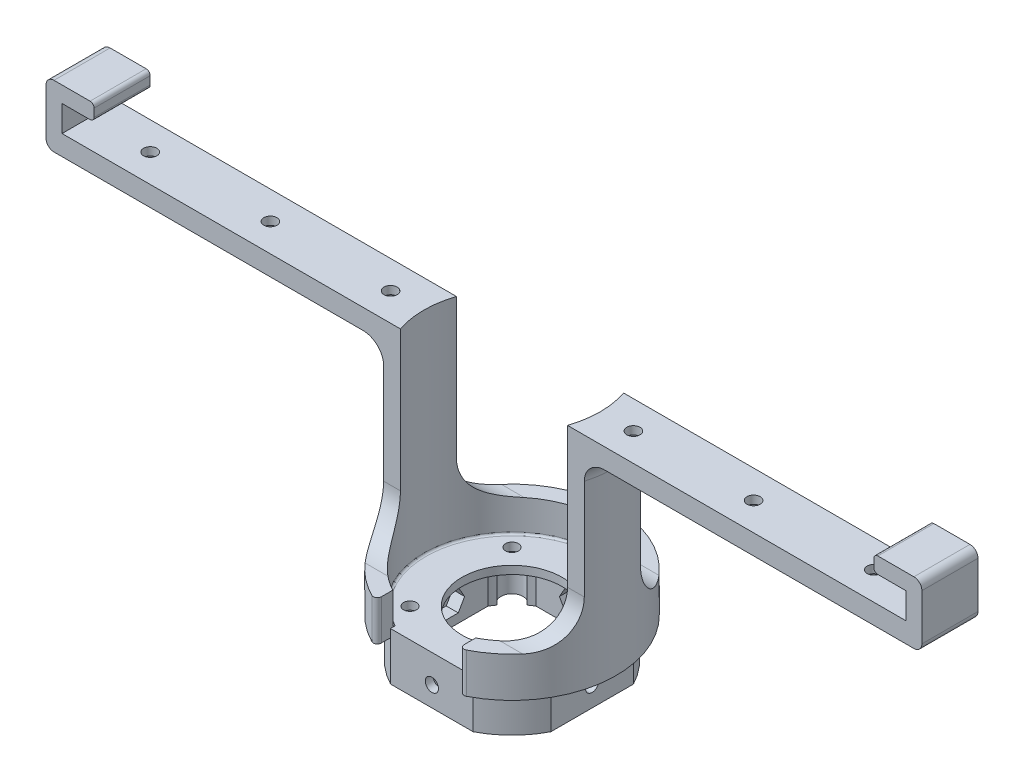
SolidWorks part; units mm, degrees
ref_plane "前视基准面" through (0, 0, 0) normal (0, 0, 1) x (1, 0, 0)
ref_plane "上视基准面" through (0, 0, 0) normal (0, 1, 0) x (1, 0, 0)
ref_plane "右视基准面" through (0, 0, 0) normal (1, 0, 0) x (0, 0, -1)
sketch "草图1" plane through (0, 0, 0) normal (0, 1, 0) x (1, 0, 0)
  line L0 (0, 0) -> (0, 18) construction
  line L1 (0, 0) -> (12.7279, 12.7279) construction
  line L2 (-32.6893, 0) -> (36.6315, 0) construction
  arc A0 (-20.3411, 8.381) -> (20.3411, 8.381) centre (0, 0) ccw
  circle A1 centre (0, 0) radius 18 construction
  circle A2 centre (12.7279, 12.7279) radius 1.6
  circle A3 centre (12.7279, -12.7279) radius 1.6
  circle A4 centre (-12.7279, -12.7279) radius 1.6
  circle A5 centre (-12.7279, 12.7279) radius 1.6
  circle A6 centre (0, 0) radius 22
  arc A7 (20.3411, 8.381) -> (-20.3411, 8.381) centre (0, 0) ccw
  point P16 (0, 0)
  dimension "D1" = 44
  dimension "D2" = 36
  dimension "D3" = 45
  dimension "D4" = 3.2
  dimension "D5" = 4
extrude "凸台-拉伸1" add sketch "草图1" along normal blind 2 contours A0 A6 A2 A3 A4 A5 region at (0, 0, 0)
sketch "草图2" plane through (0, 2, 0) normal (0, 1, 0) x (1, 0, 0)
  circle A1 centre (0, 0) radius 12.5
  dimension "D1" = 25
extrude "切除-拉伸1" cut sketch "草图2" against normal blind 3 contours A1 region at (0, 2, 0)
sketch "草图5" plane through (0, 0, 0) normal (0, 1, 0) x (1, 0, 0)
  line L6 (0, 27.5) -> (0, -27.5) construction
  circle A1 centre (0, 0) radius 22
  circle A3 centre (0, 0) radius 26
  dimension "D3" = 44
  dimension "D1" = 52
extrude "凸台-拉伸3" add sketch "草图5" along normal blind 10
sketch "草图14" plane through (0, 0, 0) normal (0, -1, 0) x (1, 0, 0)
  line L0 (-10.3078, 20) -> (10.3078, 20)
  line L1 (20, 10.3078) -> (20, -10.3078)
  line L2 (-10.3078, -20) -> (10.3078, -20)
  line L3 (-20, -10.3078) -> (-20, 10.3078)
  line L4 (-9.0139, 15) -> (9.0139, 15)
  line L5 (15, 9.0139) -> (15, -9.0139)
  line L6 (-15, 9.0139) -> (-15, -9.0139)
  line L7 (-9.0139, -15) -> (9.0139, -15)
  arc A0 (-10.3078, 20) -> (-20, 10.3078) centre (0, 0) ccw
  arc A1 (20, 10.3078) -> (10.3078, 20) centre (0, 0) ccw
  arc A2 (10.3078, -20) -> (20, -10.3078) centre (0, 0) ccw
  arc A3 (-20, -10.3078) -> (-10.3078, -20) centre (0, 0) ccw
  arc A4 (-15, -9.0139) -> (-14.1106, -10.3508) centre (0, 0) ccw
  arc A5 (-9.0139, 15) -> (-10.3508, 14.1106) centre (0, 0) ccw
  arc A6 (15, 9.0139) -> (14.1106, 10.3508) centre (0, 0) ccw
  arc A7 (9.0139, -15) -> (10.3508, -14.1106) centre (0, 0) ccw
  arc A8 (-10.3508, 14.1106) -> (-14.1106, 10.3508) centre (-12.7279, 12.7279) ccw
  arc A9 (14.1106, 10.3508) -> (10.3508, 14.1106) centre (12.7279, 12.7279) ccw
  arc A10 (-14.1106, -10.3508) -> (-10.3508, -14.1106) centre (-12.7279, -12.7279) ccw
  arc A11 (10.3508, -14.1106) -> (14.1106, -10.3508) centre (12.7279, -12.7279) ccw
  arc A12 (-14.1106, 10.3508) -> (-15, 9.0139) centre (0, 0) ccw
  arc A13 (10.3508, 14.1106) -> (9.0139, 15) centre (0, 0) ccw
  arc A14 (-10.3508, -14.1106) -> (-9.0139, -15) centre (0, 0) ccw
  arc A15 (14.1106, -10.3508) -> (15, -9.0139) centre (0, 0) ccw
  dimension "D1" = 45
  dimension "D6" = 35
  dimension "D11" = 5.5
  dimension "D12" = 5.5
  dimension "D13" = 5.5
  dimension "D14" = 5.5
  dimension "D2" = 20
  dimension "D3" = 20
  dimension "D4" = 20
  dimension "D5" = 20
  dimension "D7" = 5
  dimension "D8" = 5
  dimension "D9" = 5
  dimension "D10" = 5
extrude "凸台-拉伸5" add sketch "草图14" along normal blind 10
sketch "草图15" plane through (-20, 0, 0) normal (-1, 0, 0) x (0, 0, 1)
  line L0 (10.3078, 0) -> (-10.3078, 0) construction
  line L3 (0, 0) -> (0, -10) construction
  line L4 (10.3078, -10) -> (-10.3078, -10) construction
  circle A0 centre (0, -5) radius 1.65
  dimension "D1" = 3.3
  dimension "D2" = 5
extrude "切除-拉伸2" cut sketch "草图15" against normal blind 42
sketch "草图16" plane through (0, 0, -20) normal (0, 0, -1) x (-1, 0, 0)
  line L0 (10.3078, 0) -> (-10.3078, 0) construction
  line L1 (0, 0) -> (0, -10) construction
  line L2 (10.3078, -10) -> (-10.3078, -10) construction
  circle A0 centre (0, -5) radius 1.65
  dimension "D1" = 3.3
  dimension "D2" = 5
extrude "切除-拉伸3" cut sketch "草图16" against normal blind 42
sketch "草图18" plane through (0, 0, 0) normal (0, 0, 1) x (1, 0, 0)
  line L1 (-1.5877, -2.25) -> (-3.1754, -5)
  line L2 (-3.1754, -5) -> (-1.5877, -7.75)
  line L3 (-1.5877, -7.75) -> (1.5877, -7.75)
  line L4 (1.5877, -7.75) -> (3.1754, -5)
  line L5 (3.1754, -5) -> (1.5877, -2.25)
  line L6 (1.5877, -2.25) -> (-1.5877, -2.25)
  circle A0 centre (0, -5) radius 2.75 construction
  dimension "D1" = 5.5
extrude "切除-拉伸4" cut sketch "草图18" against normal mid plane 36
sketch "草图19" plane through (0, 0, 0) normal (1, 0, 0) x (0, 0, -1)
  line L1 (-1.5877, -2.25) -> (-3.1754, -5)
  line L2 (-3.1754, -5) -> (-1.5877, -7.75)
  line L3 (-1.5877, -7.75) -> (1.5877, -7.75)
  line L4 (1.5877, -7.75) -> (3.1754, -5)
  line L5 (3.1754, -5) -> (1.5877, -2.25)
  line L6 (1.5877, -2.25) -> (-1.5877, -2.25)
  circle A0 centre (0, -5) radius 2.75 construction
  dimension "D1" = 5.5
extrude "切除-拉伸5" cut sketch "草图19" against normal mid plane 36
sketch "草图23" plane through (0, 10, 0) normal (0, 1, 0) x (1, 0, 0)
  line L0 (-20.8567, 7) -> (-25.04, 7)
  line L1 (-26, 0) -> (26, 0) construction
  line L2 (-20.8567, -7) -> (-25.04, -7)
  line L3 (20.8567, 7) -> (25.04, 7)
  line L4 (20.8567, -7) -> (25.04, -7)
  circle A0 centre (0, 0) radius 22 construction
  circle A1 centre (0, 0) radius 26 construction
  circle A2 centre (0, 0) radius 26
  circle A3 centre (0, 0) radius 22 construction
  circle A4 centre (0, 0) radius 22
  circle M8 centre (0, 0) radius 26
  circle M9 centre (0, 0) radius 22
  dimension "D1" = 7
  dimension "D2" = 7
  dimension "D3" = 7
extrude "凸台-拉伸6" add sketch "草图23" along normal blind 45 contours L1 A4 L0 M8 | L1 A2 L2 M9 | L1 A2 L3 M9 | L1 A4 L4 M8 region at (-23.6485, 10, -3.526) region at (23.6485, 10, -3.526) region at (-23.6485, 10, 3.526) region at (23.6485, 10, 3.526)
sketch "草图24" plane through (0, 55, 0) normal (0, 1, 0) x (1, 0, 0)
  line L0 (-20.8567, 7) -> (-25.04, 7) construction
  line L1 (-25.04, -7) -> (-75.3, -7)
  line L2 (-25.04, -7) -> (-25.04, 7)
  line L3 (-25.04, 7) -> (-75.3, 7)
  line L4 (-75.3, -7) -> (-75.3, 7)
  dimension "D1" = 50.26
extrude "凸台-拉伸7" add sketch "草图24" against normal blind 5
mirror "镜向1" about plane through (0, 0, 0) normal (1, 0, 0) of "凸台-拉伸7"
sketch "草图25" plane through (0, 55, 0) normal (0, 1, 0) x (1, 0, 0)
  line L0 (-75.3, 7) -> (-75.3, -7) construction
  line L2 (-22, 0) -> (-75.3, 0) construction
  circle A0 centre (-60.3, 0) radius 1.65
  arc A1 (-20.8567, 7) -> (-20.8567, -7) centre (0, 0) ccw construction
  circle A2 centre (-30.3, 0) radius 1.65
  dimension "D1" = 3.3
  dimension "D3" = 3.3
  dimension "D2" = 15
  dimension "D4" = 30
extrude "切除-拉伸6" cut sketch "草图25" against normal blind 5
sketch "草图26" plane through (0, 50, 0) normal (0, 1, 0) x (1, 0, 0)
  line L1 (-58.7123, 2.75) -> (-61.8877, 2.75)
  line L2 (-61.8877, 2.75) -> (-63.4754, 0)
  line L3 (-63.4754, 0) -> (-61.8877, -2.75)
  line L4 (-61.8877, -2.75) -> (-58.7123, -2.75)
  line L5 (-58.7123, -2.75) -> (-57.1245, 0)
  line L6 (-57.1245, 0) -> (-58.7123, 2.75)
  line L7 (-31.8877, 2.75) -> (-33.4754, 0)
  line L8 (-33.4754, 0) -> (-31.8877, -2.75)
  line L9 (-31.8877, -2.75) -> (-28.7123, -2.75)
  line L10 (-28.7123, -2.75) -> (-27.1245, 0)
  line L11 (-27.1245, 0) -> (-28.7123, 2.75)
  line L12 (-28.7123, 2.75) -> (-31.8877, 2.75)
  circle A0 centre (-60.3, 0) radius 2.75 construction
  circle A1 centre (-30.3, 0) radius 2.75 construction
  dimension "D1" = 5.5
  dimension "D2" = 5.5
extrude "切除-拉伸7" cut sketch "草图26" along normal blind 3
mirror "镜向3" about plane through (0, 0, 0) normal (1, 0, 0) of "切除-拉伸6", "切除-拉伸7"
sketch "草图28" plane through (0, 0, 0) normal (0, -1, 0) x (1, 0, 0)
  line L0 (-10.34, 20) -> (10.34, 20)
  line L1 (10.3078, 20) -> (-10.3078, 20) construction
  line L2 (10.34, 20) -> (10.34, 23.8555)
  line L3 (-10.34, 20) -> (-10.34, 23.8555)
  line L4 (0, 26) -> (0, -26) construction
  line L5 (-26, 0) -> (26, 0) construction
  circle A0 centre (0, 0) radius 26 construction
  arc A2 (10.34, 23.8555) -> (-10.34, 23.8555) centre (0, 0) ccw
  point P4 (0, 20)
  dimension "D1" = 20.68
extrude "切除-拉伸9" cut sketch "草图28" against normal blind 10
sketch "草图29" plane through (0, 10, 0) normal (0, 1, 0) x (1, 0, 0)
  line L6 (-10.34, -20) -> (-10.34, -19.4187)
  line L7 (10.34, -20) -> (10.34, -19.4187)
  line L8 (9.1652, -20) -> (10.34, -20) construction
  line L9 (9.1652, -20) -> (10.34, -20)
  line L10 (-10.34, -20) -> (-9.1652, -20) construction
  line L11 (-10.34, -20) -> (-9.1652, -20)
  circle A6 centre (0, 0) radius 22 construction
  circle A7 centre (0, 0) radius 22 construction
  arc A8 (-10.34, -19.4187) -> (-9.1652, -20) centre (0, 0) ccw
  arc A9 (9.1652, -20) -> (10.34, -19.4187) centre (0, 0) ccw
extrude "切除-拉伸10" cut sketch "草图29" against normal blind 8
sketch "草图34" plane through (0, 50, 0) normal (0, -1, 0) x (1, 0, 0)
  line L0 (-75.3, 0) -> (75.3, 0) construction
  line L1 (-75.3, -7) -> (-105.3, -7)
  line L2 (-75.3, -7) -> (-75.3, 7)
  line L3 (-75.3, 7) -> (-105.3, 7)
  line L4 (-105.3, -7) -> (-105.3, 7)
  line L5 (75.3, -7) -> (105.3, -7)
  line L6 (75.3, -7) -> (75.3, 7)
  line L7 (75.3, 7) -> (105.3, 7)
  line L8 (105.3, -7) -> (105.3, 7)
  line L9 (-75.3, -7) -> (-75.3, 7) construction
  line L10 (75.3, -7) -> (75.3, 7) construction
  line L12 (-75.3, 7) -> (-25.04, 7) construction
  line L13 (75.3, 7) -> (25.04, 7) construction
  point P14 (-75.3, 0)
  point P17 (75.3, 0)
  dimension "D1" = 30
  dimension "D2" = 30
extrude "凸台-拉伸9" add sketch "草图34" against normal blind 5
sketch "草图35" plane through (0, 55, 0) normal (0, 1, 0) x (1, 0, 0)
  circle A0 centre (-90.3, 0) radius 1.65
  circle A1 centre (90.3, 0) radius 1.65
  circle A2 centre (-60.3, 0) radius 1.65 construction
  circle A3 centre (60.3, 0) radius 1.65 construction
  dimension "D3" = 3.3
  dimension "D4" = 3.3
  dimension "D1" = 30
  dimension "D2" = 30
extrude "切除-拉伸11" cut sketch "草图35" against normal blind 5
sketch "草图36" plane through (0, 50, 0) normal (0, -1, 0) x (1, 0, 0)
  line L1 (-91.8877, 2.75) -> (-93.4754, 0)
  line L2 (-93.4754, 0) -> (-91.8877, -2.75)
  line L3 (-91.8877, -2.75) -> (-88.7123, -2.75)
  line L4 (-88.7123, -2.75) -> (-87.1245, 0)
  line L5 (-87.1245, 0) -> (-88.7123, 2.75)
  line L6 (-88.7123, 2.75) -> (-91.8877, 2.75)
  line L7 (91.8877, 2.75) -> (88.7123, 2.75)
  line L8 (88.7123, 2.75) -> (87.1245, 0)
  line L9 (87.1245, 0) -> (88.7123, -2.75)
  line L10 (88.7123, -2.75) -> (91.8877, -2.75)
  line L11 (91.8877, -2.75) -> (93.4754, 0)
  line L12 (93.4754, 0) -> (91.8877, 2.75)
  circle A0 centre (-90.3, 0) radius 2.75 construction
  circle A1 centre (90.3, 0) radius 2.75 construction
  dimension "D1" = 5.5
  dimension "D2" = 5.5
extrude "切除-拉伸12" cut sketch "草图36" against normal blind 3
sketch "草图37" plane through (0, 50, 0) normal (0, -1, 0) x (1, 0, 0)
  line L0 (-105.3, 7) -> (-25.04, 7) construction
  line L1 (-105.3, -7) -> (-109.3, -7)
  line L2 (-105.3, -7) -> (-105.3, 7)
  line L3 (-105.3, 7) -> (-109.3, 7)
  line L4 (-109.3, -7) -> (-109.3, 7)
  line L5 (105.3, 7) -> (25.04, 7) construction
  line L6 (105.3, -7) -> (109.3, -7)
  line L7 (105.3, -7) -> (105.3, 7)
  line L8 (105.3, 7) -> (109.3, 7)
  line L9 (109.3, -7) -> (109.3, 7)
  dimension "D1" = 4
  dimension "D2" = 4
extrude "凸台-拉伸10" add sketch "草图37" against normal blind 15.5
fillet "圆角1" radius 1 2 edges at (10.34, 5, 23.8555) (-10.34, 5, 23.8555)
fillet "圆角2" radius 10 4 edges at (22.9483, 10, 7) (22.9483, 10, -7) (-22.9483, 10, -7) (-22.9483, 10, 7)
fillet "圆角3" radius 5 2 edges at (26, 50, 0) (-26, 50, 0)
sketch "草图38" plane through (-105.3, 0, 0) normal (1, 0, 0) x (0, 0, -1)
  line L0 (7, 65.5) -> (7, 55) construction
  line L1 (-7, 65.5) -> (7, 65.5)
  line L2 (-7, 65.5) -> (-7, 61.5)
  line L3 (-7, 61.5) -> (7, 61.5)
  line L4 (7, 65.5) -> (7, 61.5)
  dimension "D1" = 4
extrude "凸台-拉伸11" add sketch "草图38" along normal blind 8
sketch "草图39" plane through (105.3, 0, 0) normal (-1, 0, 0) x (0, 0, 1)
  line L0 (7, 65.5) -> (7, 55) construction
  line L1 (-7, 65.5) -> (7, 65.5)
  line L2 (-7, 65.5) -> (-7, 61.5)
  line L3 (-7, 61.5) -> (7, 61.5)
  line L4 (7, 65.5) -> (7, 61.5)
  dimension "D1" = 4
extrude "凸台-拉伸12" add sketch "草图39" along normal blind 8
fillet "圆角4" radius 1 4 edges at (97.3, 61.5, 0) (97.3, 65.5, 0) (-97.3, 61.5, 0) (-97.3, 65.5, 0)
fillet "圆角5" radius 2 4 edges at (109.3, 50, 0) (109.3, 65.5, 0) (-109.3, 50, 0) (-109.3, 65.5, 0)
fillet "圆角7" radius 0.5 7 edges at (15.9099, 0, 15.9099) (20, 0, 0) (15.9099, 0, -15.9099) (0, 0, -20) (-15.9099, 0, -15.9099) (-20, 0, 0) (-15.9099, 0, 15.9099)
fillet "圆角8" radius 0.5 1 edges at (0, 2, -22)
